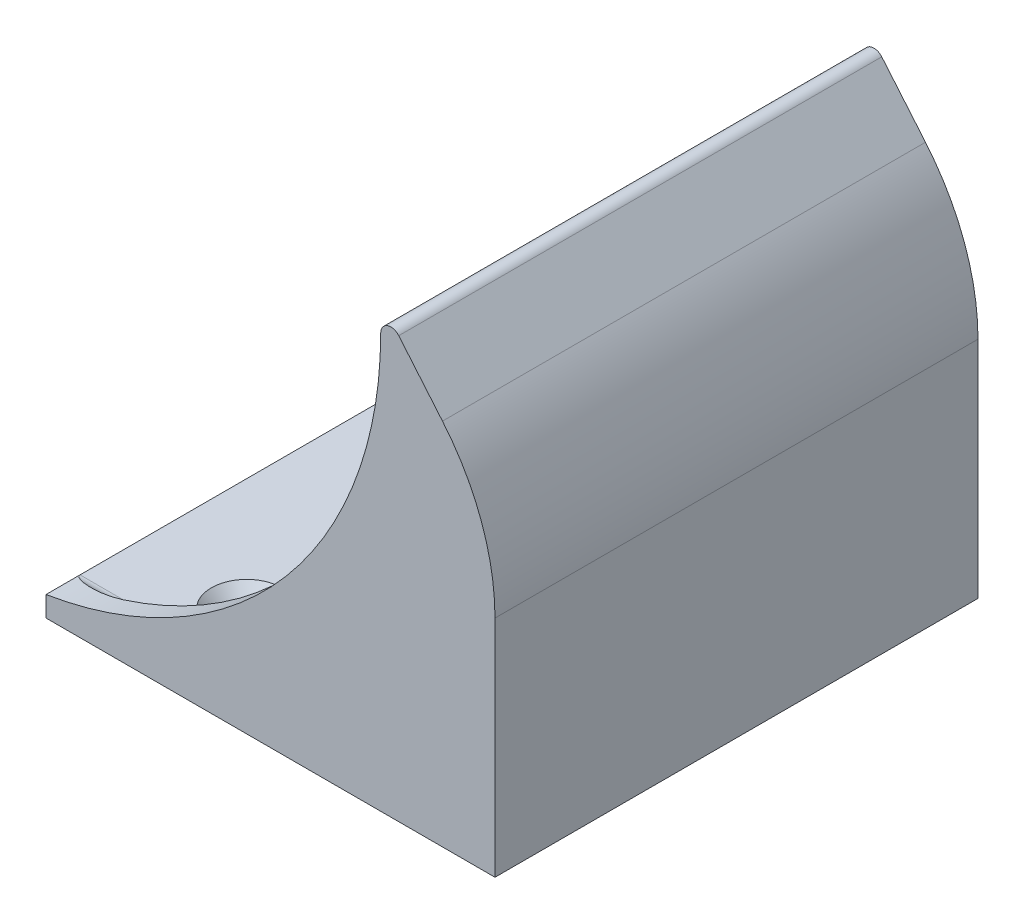
SolidWorks part; units mm, degrees
ref_plane "Front Plane" through (0, 0, 0) normal (0, 0, 1) x (1, 0, 0)
ref_plane "Top Plane" through (0, 0, 0) normal (0, 1, 0) x (1, 0, 0)
ref_plane "Right Plane" through (0, 0, 0) normal (1, 0, 0) x (0, 0, -1)
sketch "Sketch1" plane through (0, 0, 0) normal (0, 0, 1) x (1, 0, 0)
  line L0 (-38.5673, 45.9627) -> (0, 0) construction
  line L1 (-15.5859, 65.2463) -> (22.9813, 19.2836)
  line L2 (-61.5486, 26.679) -> (-22.9813, -19.2836)
  line L3 (0, 0) -> (-60, 0) construction
  line L4 (0, -30) -> (-60, -30)
  line L5 (0, 30) -> (-60, 30)
  arc A0 (-15.5859, 65.2463) -> (-61.5486, 26.679) centre (-38.5673, 45.9627) ccw
  arc A1 (-22.9813, -19.2836) -> (22.9813, 19.2836) centre (0, 0) ccw
  circle A2 centre (0, 0) radius 30 construction
  arc A3 (0, -30) -> (0, 30) centre (0, 0) ccw
  arc A4 (-60, 30) -> (-60, -30) centre (-60, 0) ccw
  circle A5 centre (0, 0) radius 33
  point P3 (-19.2836, 22.9813)
  point P10 (-30, 0)
  dimension "D1" = 60
  dimension "D3" = 3
  dimension "D2" = 50
sketch "Sketch2" plane through (0, 0, 0) normal (0, 0, 1) x (1, 0, 0)
  line L0 (22.9813, 19.2836) -> (25.2795, 21.212) construction
  line L2 (33, 0) -> (33, -33)
  line L3 (33, -33) -> (-33, -33)
  line L4 (-33, -33) -> (-33, -30)
  line L5 (-33, -30) -> (0, -30)
  line L6 (22.9813, 19.2836) -> (16.5535, 26.9441)
  line L7 (25.2795, 21.212) -> (18.8516, 28.8724)
  line L8 (16.5535, 26.9441) -> (18.8516, 28.8724) construction
  arc A0 (22.9813, 19.2836) -> (0, -30) centre (0, 0) cw
  arc A1 (-22.9813, -19.2836) -> (22.9813, 19.2836) centre (0, 0) ccw construction
  arc A2 (25.2795, 21.212) -> (33, 0) centre (0, 0) cw
  circle A3 centre (0, 0) radius 33 construction
  arc A4 (16.5535, 26.9441) -> (18.8516, 28.8724) centre (17.7025, 27.9083) cw
  dimension "D1" = 10
extrude "Boss-Extrude1" add sketch "Sketch2" along normal blind 32.5
sketch "Sketch3" plane through (0, 0, 32.5) normal (0, 0, 1) x (1, 0, 0)
  line L7 (0, -30) -> (-33, -30)
  line L8 (-33, -30) -> (-33, -33)
  line L9 (-33, -33) -> (33, -33)
  line L10 (33, -33) -> (33, 0)
  line L11 (25.2795, 21.212) -> (18.8516, 28.8724)
  line L12 (16.5535, 26.9441) -> (22.9813, 19.2836)
  line L14 (-33, -30) -> (-33, -33)
  line L15 (-33, -33) -> (33, -33)
  line L16 (33, -33) -> (33, 0)
  line L17 (25.2795, 21.212) -> (18.8516, 28.8724)
  arc A0 (18.8516, 28.8724) -> (16.5535, 26.9441) centre (17.7025, 27.9083) ccw construction
  arc A1 (-33, -30) -> (16.2025, 27.9083) centre (-42.4759, 27.9083) ccw
  arc A4 (0, -30) -> (22.9813, 19.2836) centre (0, 0) ccw
  arc A5 (33, 0) -> (25.2795, 21.212) centre (0, 0) ccw
  arc A6 (18.8516, 28.8724) -> (16.5535, 26.9441) centre (17.7025, 27.9083) ccw
  arc A8 (33, 0) -> (25.2795, 21.212) centre (0, 0) ccw
  arc A9 (18.8516, 28.8724) -> (16.2025, 27.9083) centre (17.7025, 27.9083) ccw
  point P10 (0, 0)
  point P15 (0, 0)
  dimension "D1" = 0
extrude "Boss-Extrude2" add sketch "Sketch3" along normal blind 3
sketch "Sketch4" plane through (0, -30, 0) normal (0, 1, 0) x (1, 0, 0)
  line L0 (-16.5, -32.5) -> (-16.5, -22.5) construction
  line L1 (0, -32.5) -> (-33, -32.5) construction
  dimension "D1" = 10
hole_wizard "CSK for M5 Flat Head Machine Screw1" positions "3DSketch1" profile "Sketch5" countersink size "M5" standard "ANSI Metric" end condition through all
sketch3d "3DSketch1"
  point P0 (-16.5, -30, 22.5)
sketch "Sketch5" plane through (-16.5, -30, 22.5) normal (1, 0, 0) x (0, 0, 1)
  line L0 (0, 0) -> (0, 3)
  line L1 (0, 3) -> (2.9, 3)
  line L2 (2.9, 3) -> (2.9, 2.3)
  line L3 (2.9, 2.3) -> (5.2, 0)
  line L5 (5.2, 0) -> (0, 0)
  line L6 (-2.9, 2.3) -> (-5.2, 0) construction
  line L11 (0, -6.35) -> (0, 107.95) construction
  dimension "Thru Hole Dia." = 5.8
  dimension "Thru Hole Depth" = 3
  dimension "Near C'Sink Dia." = 10.4
  dimension "Near C'Sink Angle" = 90
fillet "Fillet1" radius 2 4 edges at (16.293, 27.3952, 32.5) (19.7674, 23.1139, 32.5) (-16.5, -30, 32.5) (27.1892, -12.6785, 32.5)
mirror "Mirror1" about plane through (0, 0, 0) normal (0, 0, -1) of bodies 103
